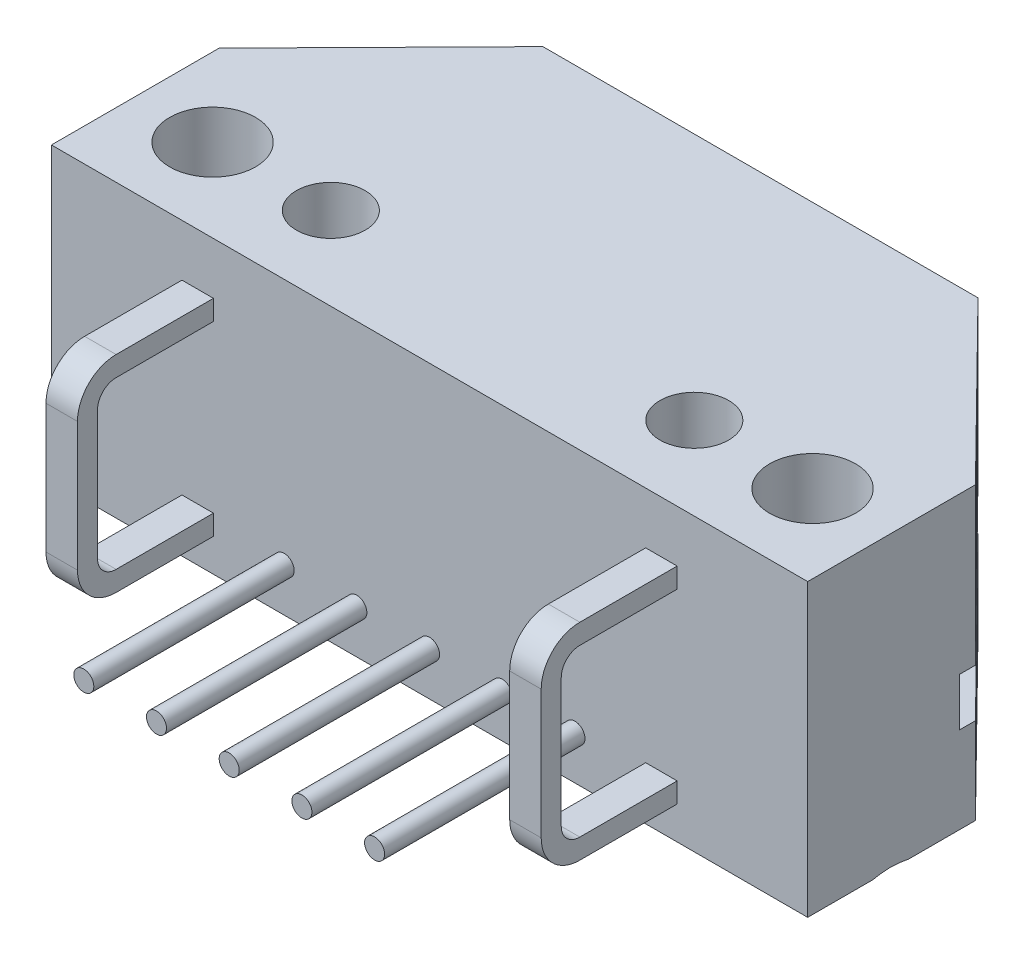
SolidWorks part; units mm, degrees
ref_plane "Ebene vorne" through (0, 0, 0) normal (0, 0, 1) x (1, 0, 0)
ref_plane "Ebene oben" through (0, 0, 0) normal (0, 1, 0) x (1, 0, 0)
ref_plane "Ebene rechts" through (0, 0, 0) normal (1, 0, 0) x (0, 0, -1)
sketch "Skizze1" plane through (0, 0, 0) normal (0, 1, 0) x (1, 0, 0)
  line L0 (0, 18.4765) -> (0, -25.5527) construction
  line L1 (-10.8738, -15.75) -> (10.2359, -15.75) construction
  line L2 (-12.2657, 0) -> (14.2955, 0) construction
  line L3 (-13.21, -18.65) -> (-13.21, -12.79)
  line L4 (-13.21, -12.79) -> (-7.6, -7.09)
  line L5 (-7.6, -7.09) -> (7.6, -7.09)
  line L6 (-13.21, -18.65) -> (13.21, -18.65)
  line L7 (13.21, -18.65) -> (13.21, -12.79)
  line L8 (13.21, -12.79) -> (7.6, -7.09)
  circle A0 centre (-10.48, -15.75) radius 1.385
  circle A1 centre (10.48, -15.75) radius 1.385
  point P17 (0, -18.65)
  point P19 (0, -7.09)
  dimension "D2" = 2.77
  dimension "D1" = 15.75
  dimension "D3" = 26.42
  dimension "D4" = 11.56
  dimension "D5" = 5.7
  dimension "D6" = 15.2
  dimension "D7" = 2.9
  dimension "D8" = 20.96
extrude "Aufsatz-Linear austragen1" add sketch "Skizze1" along normal blind 6.74 and the other way blind 3.42
sketch "Skizze2" plane through (0, 0, 0) normal (1, 0, 0) x (0, 0, -1)
  line L0 (-22.1031, 0) -> (8.1421, 0) construction
  line L1 (-13.35, 1.28) -> (2.6852, 1.28)
  line L2 (-13.35, 1.28) -> (-13.35, -0.4)
  line L3 (-13.35, -0.4) -> (2.6852, -0.4)
  line L4 (2.6852, 1.28) -> (2.6852, -0.4)
  line L5 (-7.09, -3.42) -> (-12.79, -3.42) construction
  line L6 (-7.09, 6.74) -> (-12.79, 6.74) construction
  line L7 (-18.65, -3.42) -> (-18.65, 6.74) construction
  dimension "D1" = 3.02
  dimension "D2" = 5.46
  dimension "D3" = 1.68
  dimension "D4" = 5.3
extrude "Schnitt-Linear austragen1" cut sketch "Skizze2" against normal through all and the other way through all
sketch "Skizze3" plane through (0, 6.74, 0) normal (0, 1, 0) x (1, 0, 0)
  line L0 (0, -26.155) -> (0, 11.9895) construction
  line L1 (21.4405, 0) -> (-13.3752, 0) construction
  line L2 (-13.21, -18.65) -> (13.21, -18.65) construction
  circle A0 centre (6.35, -15.75) radius 1.2
  circle A1 centre (-6.35, -15.75) radius 1.2
  dimension "D3" = 2.4
  dimension "D1" = 12.7
  dimension "D2" = 2.9
extrude "Schnitt-Linear austragen2" cut sketch "Skizze3" against normal blind 2.16
sketch "Skizze4" plane through (0, 0, 18.65) normal (0, 0, 1) x (1, 0, 0)
  line L0 (0, -9.3032) -> (0, 8.8775) construction
  line L1 (0, -1.9) -> (8.502, -1.9) construction
  line L2 (-13.21, -3.42) -> (13.21, -3.42) construction
  circle A0 centre (0, -1.9) radius 0.35
  circle A1 centre (2.54, -1.9) radius 0.35
  circle A2 centre (5.08, -1.9) radius 0.35
  circle A3 centre (-2.54, -1.9) radius 0.35
  circle A4 centre (-5.08, -1.9) radius 0.35
  dimension "D1" = 0.7
  dimension "D2" = 2.54
  dimension "D3" = 2.54
  dimension "D4" = 1.52
extrude "Aufsatz-Linear austragen2" add sketch "Skizze4" along normal blind 7
ref_plane "Ebene1" through (8.1, 0, 0) normal (1, 0, 0) x (0, 0, -1)
sketch "Skizze5" plane through (8.1, 0, 0) normal (1, 0, 0) x (0, 0, -1)
  line L0 (-18.65, -1.92) -> (-22.05, -1.92)
  line L1 (-23.05, -0.92) -> (-23.05, 3.58)
  line L2 (-22.05, 4.58) -> (-18.65, 4.58)
  line L3 (-18.65, -3.42) -> (-18.65, 6.74) construction
  line L4 (-18.65, -3.42) -> (-12.79, -3.42) construction
  arc A0 (-22.05, 4.58) -> (-23.05, 3.58) centre (-22.05, 3.58) ccw
  arc A1 (-23.05, -0.92) -> (-22.05, -1.92) centre (-22.05, -0.92) ccw
  point P10 (-23.05, 4.58)
  point P13 (-23.05, -1.92)
  dimension "D4" = 1
  dimension "D1" = 1.5
  dimension "D2" = 6.5
  dimension "D3" = 4.4
extrude "Linear-Austragen-Dünn1" add sketch "Skizze5" along normal blind 0.55 and the other way blind 0.55 thin thin type mid plane wall 0.7
mirror "Spiegeln1" about plane through (0, 0, 0) normal (1, 0, 0) of "Linear-Austragen-Dünn1"
ref_axis "Achse1" through (0, -4.0534, 0) along (0, 1, 0)
hole_wizard "Formsenkung für M3 Senkschraube mit Schlitz/Kreuzschlitz1" positions "Skizze7" profile "Skizze6" countersink size "M3" standard "ANSI Metrisch"
sketch "Skizze7" plane through (0, -3.42, 0) normal (0, -1, 0) x (-1, 0, 0)
  point P0 (-10.48, -15.75)
  point P3 (10.48, -15.75)
sketch "Skizze6" plane through (10.48, -3.42, 15.75) normal (1, 0, 0) x (0, 0, -1)
  line L0 (0, 0) -> (0, 11.9013)
  line L1 (0, 11.9013) -> (1.5, 11)
  line L2 (1.5, 11) -> (1.5, 1.3)
  line L3 (1.5, 1.3) -> (2.8, 0)
  line L5 (2.8, 0) -> (0, 0)
  line L6 (-1.5, 1.3) -> (-2.8, 0) construction
  line L10 (0, 11.9013) -> (-1.5, 11) construction
  line L11 (0, -6.35) -> (0, 107.95) construction
  dimension "Bohrerdurchmesser" = 3
  dimension "Bohrungstiefe" = 11
  dimension "Senkdurchmesser (Oben)" = 5.6
  dimension "Senkwinkel (Oben)" = 90
  dimension "Spitzenwinkel" = 118
